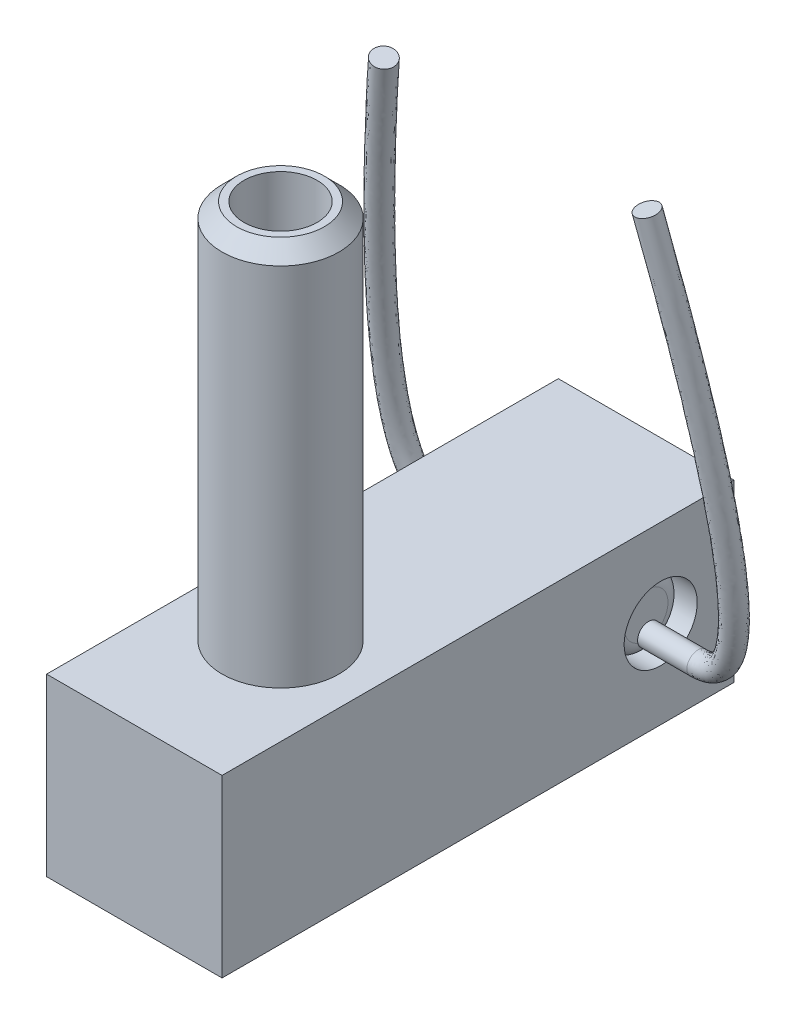
SolidWorks part; units mm, degrees
other "8-Omx6Wt"
other "PEEK-D8"
other "Alu-12x12"
other "Alu-D8"
material "PE mit sehr geringer Dichte PE (SS)"
material "3.0205 (EN AW-1200)"
ref_plane "Ebene vorne" through (0, 0, 0) normal (0, 0, 1) x (1, 0, 0)
ref_plane "Ebene oben" through (0, 0, 0) normal (0, 1, 0) x (1, 0, 0)
ref_plane "Ebene rechts" through (0, 0, 0) normal (1, 0, 0) x (0, 0, -1)
sketch "Skizze1" plane through (0, 0, 0) normal (0, 0, 1) x (1, 0, 0)
  line L1 (6, -6) -> (-6, -6)
  line L2 (6, -6) -> (6, 6)
  line L3 (6, 6) -> (-6, 6)
  line L4 (-6, -6) -> (-6, 6)
  line L5 (6, -6) -> (-6, 6) construction
  line L6 (6, 6) -> (-6, -6) construction
  point P0 (0, 0)
  dimension "D1" = 12
extrude "Aufsatz-Linear austragen1" add sketch "Skizze1" along normal blind 35
sketch "Skizze2" plane through (-6, 0, 0) normal (-1, 0, 0) x (0, 0, 1)
  line L0 (0, 6) -> (0, -6) construction
  circle A0 centre (5, 0) radius 2.5
  point P2 (0, 0)
  dimension "D1" = 5
  dimension "D2" = 5
extrude "Schnitt-Linear austragen1" cut sketch "Skizze2" against normal blind 35
hole_wizard "M8 Gewindebohrung1" positions "Skizze5" profile "Skizze4" tap size "M8" standard "DIN" end condition through all
sketch "Skizze5" plane through (0, 6, 0) normal (0, 1, 0) x (-1, 0, 0)
  line L0 (-6, 35) -> (6, 35) construction
  point P0 (0, 25)
  point P4 (0, 35)
  dimension "D1" = 10
sketch "Skizze4" plane through (0, 6, 25) normal (1, 0, 0) x (0, 0, 1)
  line L0 (0, 0) -> (0, 12)
  line L1 (0, 12) -> (3.4, 12)
  line L2 (3.4, 12) -> (3.4, 0)
  line L5 (3.4, 0) -> (0, 0)
  line L11 (0, -6.35) -> (0, 107.95) construction
  dimension "Bohrerdurchmesser" = 6.8
  dimension "Bohrungstiefe" = 12
cosmetic thread "Bohrungsgewinde1"
sketch "Skizze7" plane through (0, 0, 0) normal (1, 0, 0) x (0, 0, -1)
  line L0 (-25, 2) -> (-25, -10) construction
  line L1 (-25, -10) -> (-29, -10) construction
  line L2 (-29, 2) -> (-26.5, 2)
  line L3 (-29, -10) -> (-29, 2)
  line L4 (-29, 2) -> (-25, 2) construction
  line L5 (-35, -6) -> (0, -6) construction
  line L6 (-26.5, 2) -> (-26.5, -8.5)
  line L7 (-26.5, -8.5) -> (-25.25, -8.5)
  line L8 (-25.25, -8.5) -> (-25.25, -10)
  line L9 (-25.25, -10) -> (-29, -10)
  dimension "D1" = 8
  dimension "D2" = 8
  dimension "D3" = 12
  dimension "D4" = 0.5
  dimension "D5" = 3
  dimension "D6" = 1.5
revolve "Rotation1" add sketch "Skizze7" angle 360 about L0
cosmetic thread "Gewindedarstellung1"
chamfer "Fase1" distance 3 angle 45 1 edges at (0, -10, 29)
fillet "Verrundung2" radius 1 1 edges at (0, -7, 21)
sketch "Skizze8" plane through (0, 2, 0) normal (0, 1, 0) x (1, 0, 0)
  circle A0 centre (0, -25) radius 2.5
  circle A1 centre (0, -25) radius 4
  circle A2 centre (0, -25) radius 4
  dimension "D2" = 5
  dimension "D1" = 0
extrude "Aufsatz-Linear austragen2" add sketch "Skizze8" along normal blind 30 separate body
cosmetic thread "Gewindedarstellung2"
chamfer "Fase2" distance 1 angle 45 2 edges at (0, 2, 29) (0, 32, 29)
sketch "Skizze9" plane through (0, 0, 0) normal (1, 0, 0) x (0, 0, -1)
  circle A0 centre (-5, 0) radius 2.5
  dimension "D1" = 5
extrude "Aufsatz-Linear austragen3" add sketch "Skizze9" along normal mid plane 10 separate body
fillet "Verrundung3" radius 1 2 edges at (5, 0, 2.5) (-5, 0, 2.5)
ref_axis "Achse1" through (6, 0, 5) along (-1, 0, 0)
ref_plane "Ebene1" through (0, -0.6891, 4.9032) normal (0, 0.1392, -0.9903) x (-1, 0, 0)
sketch "Skizze10" plane through (0, -0.6891, 4.9032) normal (0, 0.1392, -0.9903) x (-1, 0, 0)
  line L0 (-8.3745, -0.5306) -> (8.3745, -0.5306)
  line L1 (0, -0.5306) -> (0, 6.0164) construction
  spline S0 degree 2 poles (8.3745, -0.5306) (14.661, -0.5306) (9.0031, 28.9529) knots 0 0 0 1 1 1
  spline S1 degree 2 poles (-8.3745, -0.5306) (-14.661, -0.5306) (-9.0031, 28.9529) knots 0 0 0 1 1 1
ref_plane "Ebene2" through (9.0031, 27.9821, 8.9326) normal (-0.1885, 0.9725, 0.1367) x (-0.9804, -0.1781, -0.0844)
sketch "Skizze11" plane through (9.0031, 27.9821, 8.9326) normal (-0.1885, 0.9725, 0.1367) x (-0.9804, -0.1781, -0.0844)
  circle A0 centre (0, 0) radius 0.75
  dimension "D1" = 1.5
sweep "Austragung1" add profiles "Skizze11" path "Skizze10"
